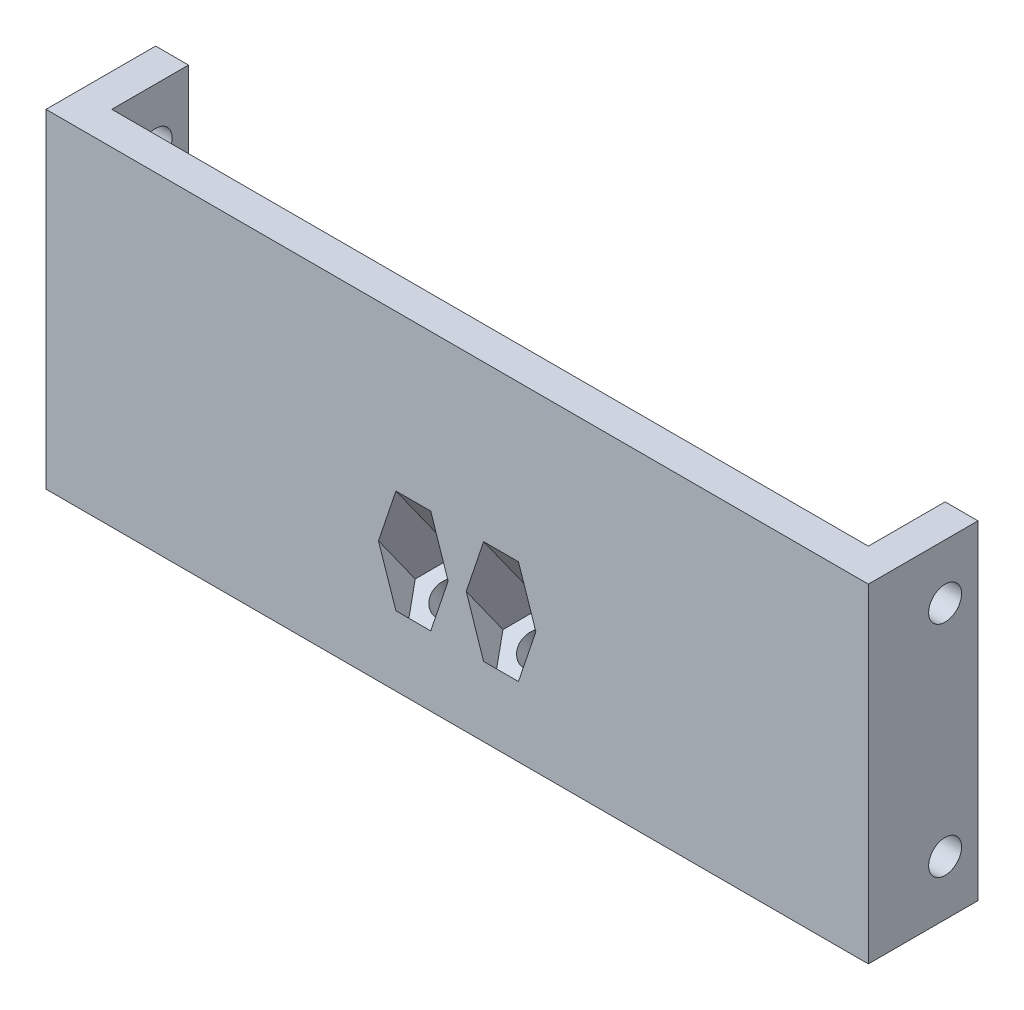
SolidWorks part; units mm, degrees
ref_plane "Front Plane" through (0, 0, 0) normal (0, 0, 1) x (1, 0, 0)
ref_plane "Top Plane" through (0, 0, 0) normal (0, 1, 0) x (1, 0, 0)
ref_plane "Right Plane" through (0, 0, 0) normal (1, 0, 0) x (0, 0, -1)
sketch "Sketch1" plane through (0, 0, 0) normal (0, 0, 1) x (1, 0, 0)
  line L1 (-37.5, -15) -> (37.5, -15)
  line L2 (-37.5, -15) -> (-37.5, 15)
  line L3 (-37.5, 15) -> (37.5, 15)
  line L4 (37.5, -15) -> (37.5, 15)
  line L5 (-37.5, -15) -> (37.5, 15) construction
  line L6 (-37.5, 15) -> (37.5, -15) construction
  point P0 (0, 0)
  dimension "D1" = 30
  dimension "D2" = 75
extrude "Boss-Extrude1" add sketch "Sketch1" along normal blind 3
sketch "Sketch2" plane through (0, 0, 0) normal (0, 0, -1) x (-1, 0, 0)
  line L0 (-37.5, -15) -> (-37.5, 15) construction
  line L1 (-34.5, -15) -> (-37.5, -15)
  line L2 (-34.5, -15) -> (-34.5, 15)
  line L3 (-34.5, 15) -> (-37.5, 15)
  line L4 (-37.5, -15) -> (-37.5, 15)
  line L5 (-34.5, -15) -> (-37.5, 15) construction
  line L6 (-34.5, 15) -> (-37.5, -15) construction
  line L7 (-37.5, 15) -> (37.5, 15) construction
  line L8 (37.5, -15) -> (-37.5, -15) construction
  point P0 (-36, 0)
  dimension "D1" = 0
  dimension "D2" = 0
  dimension "D3" = 3
extrude "Boss-Extrude2" add sketch "Sketch2" along normal blind 7
sketch "Sketch4" plane through (34.5, 0, 0) normal (-1, 0, 0) x (0, 0, 1)
  line L0 (-7, 15) -> (0, 15) construction
  line L1 (-7, -15) -> (-7, 15) construction
  line L2 (0, -15) -> (0, 15) construction
  circle A0 centre (-4, 10) radius 1.5
  dimension "D1" = 3
  dimension "D2" = 5
  dimension "D3" = 3
extrude "Cut-Extrude1" cut sketch "Sketch4" against normal blind 3
mirror "Mirror2" about plane through (0, 0, 0) normal (0, 1, 0) of "Cut-Extrude1"
mirror "Mirror1" about plane through (0, 0, 0) normal (1, 0, 0) of "Mirror2", "Cut-Extrude1", "Boss-Extrude2"
sketch "Sketch5" plane through (0, -15, 0) normal (0, -1, 0) x (1, 0, 0)
  line L0 (-34.5, 0) -> (34.5, 0) construction
  line L1 (-8, 0) -> (8, 0)
  line L2 (-8, 0) -> (-8, -7)
  line L3 (-8, -7) -> (8, -7)
  line L4 (8, 0) -> (8, -7)
  line L5 (34.5, -7) -> (34.5, 0) construction
  dimension "D1" = 16
  dimension "D2" = 26.5
extrude "Boss-Extrude3" add sketch "Sketch5" against normal blind 8
chamfer "Chamfer1" distance 5 distance2 7 1 edges at (0, -15, -7) first distance on face at (0, -11, -7)
chamfer "Chamfer2" distance 5 angle 45 1 edges at (0, -7, 0)
chamfer "Chamfer3" distance 2 angle 45 1 edges at (0, -7, -7)
sketch "Sketch6" plane through (0, -9.9324, -7.0946) normal (0, -0.8137, -0.5812) x (1, 0, 0)
  line L0 (8, 8.7186) -> (8, 0.1162) construction
  line L1 (-8, 0.1162) -> (-8, 8.7186) construction
  line L2 (-8, 8.7186) -> (8, 8.7186) construction
  circle A0 centre (-4, 4.7186) radius 1.5
  circle A1 centre (4, 4.7186) radius 1.5
  dimension "D1" = 3
  dimension "D2" = 3
  dimension "D3" = 4
  dimension "D4" = 4
  dimension "D5" = 4
  dimension "D6" = 4
extrude "Cut-Extrude2" cut sketch "Sketch6" against normal blind 8
sketch "Sketch7" plane through (0, -9.9324, -7.0946) normal (0, -0.8137, -0.5812) x (1, 0, 0)
  line L1 (-0.8246, 4.7186) -> (-2.4123, 7.4686)
  line L2 (-2.4123, 7.4686) -> (-5.5877, 7.4686)
  line L3 (-5.5877, 7.4686) -> (-7.1754, 4.7186)
  line L4 (-7.1754, 4.7186) -> (-5.5877, 1.9686)
  line L5 (-5.5877, 1.9686) -> (-2.4123, 1.9686)
  line L6 (-2.4123, 1.9686) -> (-0.8246, 4.7186)
  line L7 (7.1754, 4.7186) -> (5.5877, 7.4686)
  line L8 (5.5877, 7.4686) -> (2.4123, 7.4686)
  line L9 (2.4123, 7.4686) -> (0.8246, 4.7186)
  line L10 (0.8246, 4.7186) -> (2.4123, 1.9686)
  line L11 (2.4123, 1.9686) -> (5.5877, 1.9686)
  line L12 (5.5877, 1.9686) -> (7.1754, 4.7186)
  circle A0 centre (-4, 4.7186) radius 2.75 construction
  circle A1 centre (4, 4.7186) radius 2.75 construction
  dimension "D1" = 5.5
  dimension "D2" = 5.5
extrude "Cut-Extrude3" cut sketch "Sketch7" against normal through all from offset 5 offset against normal yes
equation "\"D2@Sketch5\"=\"D2@Sketch1\"/2-\"D3@Sketch2\"-\"D1@Sketch5\"/2"
equation "\"D2@Sketch6\"=\"D1@Sketch6\""
equation "\"D4@Sketch6\"=\"D3@Sketch6\""
equation "\"D6@Sketch6\"=\"D5@Sketch6\""
